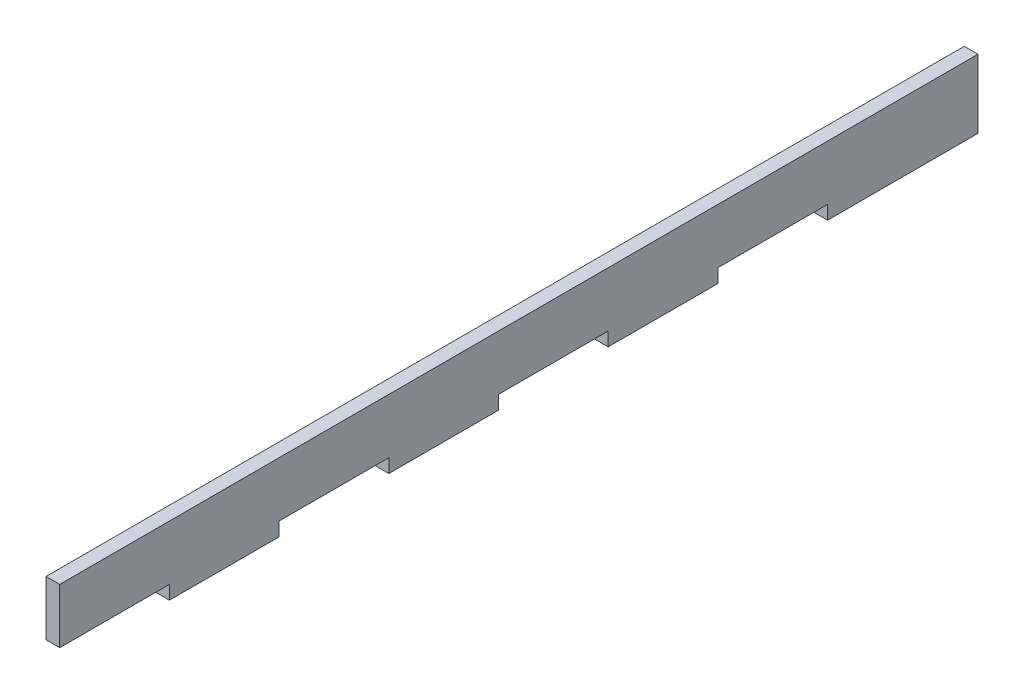
SolidWorks part; units mm, degrees
ref_plane "Front Plane" through (0, 0, 0) normal (0, 0, 1) x (1, 0, 0)
ref_plane "Top Plane" through (0, 0, 0) normal (0, 1, 0) x (1, 0, 0)
ref_plane "Right Plane" through (0, 0, 0) normal (1, 0, 0) x (0, 0, -1)
sketch "Sketch2" plane through (0, 0, 0) normal (1, 0, 0) x (0, 0, -1)
  line L30 (48.3194, 0) -> (99.1194, 0)
  line L31 (-2.4806, 6.35) -> (-2.4806, 31.75)
  line L32 (-2.4806, 31.75) -> (422.7895, 31.75)
  line L33 (422.7895, 0) -> (422.7895, 31.75)
  line L34 (353.1194, 6.35) -> (353.1194, 0) construction
  line L35 (302.3194, 6.35) -> (353.1194, 6.35) construction
  line L36 (302.3194, 6.35) -> (302.3194, 0) construction
  line L37 (251.5194, 6.35) -> (251.5194, 0) construction
  line L38 (200.7194, 6.35) -> (251.5194, 6.35) construction
  line L39 (200.7194, 6.35) -> (200.7194, 0) construction
  line L40 (149.9194, 6.35) -> (149.9194, 0) construction
  line L41 (99.1194, 6.35) -> (149.9194, 6.35) construction
  line L42 (99.1194, 6.35) -> (99.1194, 0) construction
  line L43 (48.3194, 6.35) -> (48.3194, 0) construction
  line L44 (-2.4806, 6.35) -> (48.3194, 6.35) construction
  line L45 (422.7895, 31.75) -> (422.7895, 35.3357) construction
  line L46 (353.1194, 6.35) -> (353.1194, 0)
  line L47 (302.3194, 6.35) -> (353.1194, 6.35)
  line L48 (302.3194, 6.35) -> (302.3194, 0)
  line L49 (251.5194, 6.35) -> (251.5194, 0)
  line L50 (200.7194, 6.35) -> (251.5194, 6.35)
  line L51 (200.7194, 6.35) -> (200.7194, 0)
  line L52 (149.9194, 6.35) -> (149.9194, 0)
  line L53 (99.1194, 6.35) -> (149.9194, 6.35)
  line L54 (99.1194, 6.35) -> (99.1194, 0)
  line L55 (48.3194, 6.35) -> (48.3194, 0)
  line L56 (-2.4806, 6.35) -> (48.3194, 6.35)
  line L57 (353.1194, 0) -> (422.7895, 0)
  line L58 (251.5194, 0) -> (302.3194, 0)
  line L59 (149.9194, 0) -> (200.7194, 0)
  point P0 (408.1494, 47.2143)
extrude "Boss-Extrude1" add sketch "Sketch2" along normal blind 6.35
